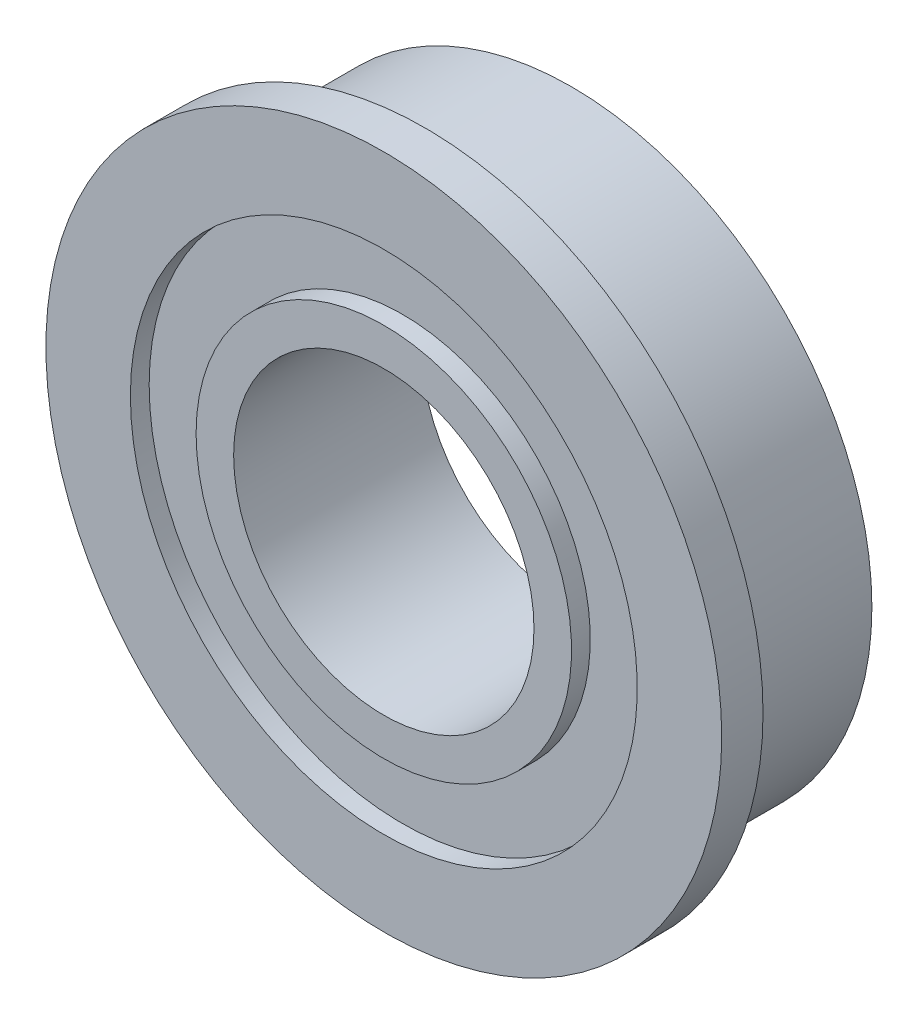
SolidWorks part; units mm, degrees
ref_plane "Front Plane" through (0, 0, 0) normal (0, 0, 1) x (1, 0, 0)
ref_plane "Top Plane" through (0, 0, 0) normal (0, 1, 0) x (1, 0, 0)
ref_plane "Right Plane" through (0, 0, 0) normal (1, 0, 0) x (0, 0, -1)
sketch "Sketch1" plane through (0, 0, 0) normal (0, 0, 1) x (1, 0, 0)
  circle A0 centre (0, 0) radius 8
  dimension "D1" = 16
extrude "Boss-Extrude1" add sketch "Sketch1" along normal blind 3.9
sketch "Sketch2" plane through (0, 0, 3.9) normal (0, 0, 1) x (1, 0, 0)
  circle A0 centre (0, 0) radius 9
  dimension "D1" = 18
extrude "Boss-Extrude2" add sketch "Sketch2" along normal blind 1.1
sketch "Sketch3" plane through (0, 0, 0) normal (0, 0, -1) x (-1, 0, 0)
  circle A0 centre (0, 0) radius 5
  circle A1 centre (0, 0) radius 6.75
  circle A2 centre (0, 0) radius 4
  dimension "D1" = 13.5
  dimension "D2" = 10
  dimension "D3" = 8
extrude "Cut-Extrude1" cut sketch "Sketch3" against normal blind 0.5 contours A1 A0 region at (6.5591, 0, 0)
extrude "Cut-Extrude2" cut sketch "Sketch3<3>" against normal through all contours A2 region at (0, 0, 0)
sketch "Sketch3<3>" plane through (0, 0, 0) normal (0, 0, -1) x (-1, 0, 0) same geometry as "Sketch3"
ref_plane "Plane1" through (0, 0, 2.5) normal (0, 0, -1) x (-1, 0, 0)
mirror "Mirror1" about plane through (0, 0, 2.5) normal (0, 0, -1) of "Cut-Extrude1"
move or copy body "Body-Move/Copy1" [suppressed] bodies to move or copy 105
